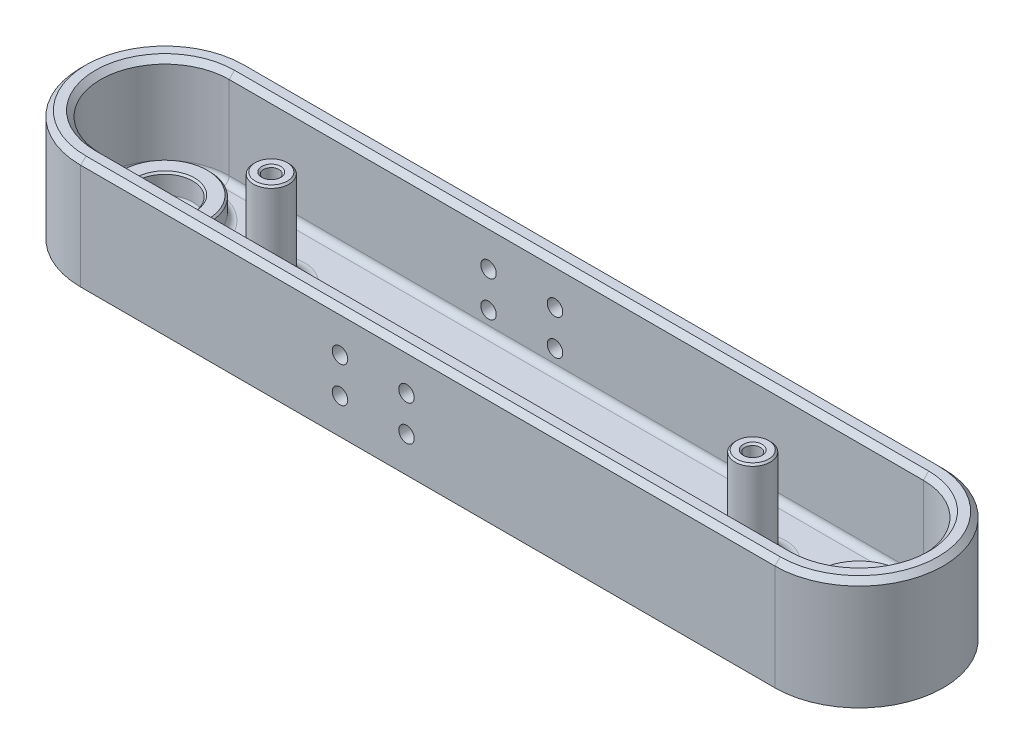
SolidWorks part; units mm, degrees
material "PLA"
ref_plane "Front Plane" through (0, 0, 0) normal (0, 0, 1) x (1, 0, 0)
ref_plane "Top Plane" through (0, 0, 0) normal (0, 1, 0) x (1, 0, 0)
ref_plane "Right Plane" through (0, 0, 0) normal (1, 0, 0) x (0, 0, -1)
sketch "Sketch1" plane through (0, 0, 0) normal (0, 1, 0) x (1, 0, 0)
  line L0 (-99.441, 0) -> (99.441, 0) construction
  line L1 (0, -55.9739) -> (0, 55.9739) construction
  line L2 (-99.441, 24.13) -> (99.441, 24.13)
  line L3 (-99.441, -24.13) -> (99.441, -24.13)
  arc A0 (-99.441, 24.13) -> (-99.441, -24.13) centre (-99.441, 0) ccw
  arc A1 (99.441, 24.13) -> (99.441, -24.13) centre (99.441, 0) cw
  point P4 (0, 0)
  point P10 (0, 0)
  dimension "D2" = 48.26
  dimension "D1" = 198.882
extrude "MainBlock" add sketch "Sketch1" along normal blind 31.75
sketch "Sketch2" plane through (0, 31.75, 0) normal (0, 1, 0) x (1, 0, 0)
  line L0 (0, 0) -> (155.7407, 0) construction
  line L1 (0, 0) -> (0, 57.4416) construction
  line L2 (-99.441, -24.13) -> (99.441, -24.13) construction
  line L3 (99.441, 24.13) -> (-99.441, 24.13) construction
  line L4 (-99.441, -24.13) -> (99.441, -24.13) construction
  line L5 (99.441, 24.13) -> (-99.441, 24.13) construction
  line L6 (-99.441, 18.415) -> (99.441, 18.415)
  line L7 (-99.441, -18.415) -> (99.441, -18.415)
  arc A0 (99.441, -24.13) -> (99.441, 24.13) centre (99.441, 0) ccw construction
  arc A1 (-99.441, 24.13) -> (-99.441, -24.13) centre (-99.441, 0) ccw construction
  arc A2 (99.441, -24.13) -> (99.441, 24.13) centre (99.441, 0) ccw construction
  arc A3 (-99.441, 24.13) -> (-99.441, -24.13) centre (-99.441, 0) ccw construction
  arc A4 (-99.441, 18.415) -> (-99.441, -18.415) centre (-99.441, 0) ccw
  arc A5 (99.441, 18.415) -> (99.441, -18.415) centre (99.441, 0) cw
  point P18 (0, 18.415)
  point P19 (0, -18.415)
  dimension "D1" = 5.715
extrude "MainPocket" cut sketch "Sketch2" against normal offset from surface (27.305 mm away) 4.445 up to face at (0, 0, 0)
sketch "Sketch3" plane through (0, 0, 0) normal (0, -1, 0) x (1, 0, 0)
  line L2 (-99.441, -24.13) -> (99.441, -24.13)
  line L3 (99.441, 24.13) -> (-99.441, 24.13)
  line L4 (-99.441, -24.13) -> (99.441, -24.13) construction
  line L5 (99.441, 24.13) -> (-99.441, 24.13) construction
  circle A0 centre (-99.441, 0) radius 4.445
  circle A1 centre (99.441, 0) radius 4.445
  arc A2 (-99.441, 24.13) -> (-99.441, -24.13) centre (-99.441, 0) ccw
  arc A3 (99.441, -24.13) -> (99.441, 24.13) centre (99.441, 0) ccw
  arc A4 (-99.441, 24.13) -> (-99.441, -24.13) centre (-99.441, 0) ccw construction
  arc A5 (99.441, -24.13) -> (99.441, 24.13) centre (99.441, 0) ccw construction
  dimension "D2" = 8.89
  dimension "D3" = 8.89
  dimension "D1" = 0
extrude "Cut-Extrude1" cut sketch "Sketch3" against normal through all
sketch "Sketch4" plane through (0, 4.445, 0) normal (0, 1, 0) x (1, 0, 0)
  line L0 (0, 0) -> (50000, 0) construction
  line L1 (0, 0) -> (0, 50000) construction
  line L2 (99.441, 18.415) -> (-99.441, 18.415)
  line L3 (-99.441, -18.415) -> (99.441, -18.415)
  line L4 (99.441, 18.415) -> (-99.441, 18.415) construction
  line L5 (-99.441, -18.415) -> (99.441, -18.415) construction
  circle A0 centre (-99.441, 0) radius 7.9566
  circle A1 centre (-99.441, 0) radius 12.7
  arc A2 (99.441, -18.415) -> (99.441, 18.415) centre (99.441, 0) ccw
  arc A3 (-99.441, 18.415) -> (-99.441, -18.415) centre (-99.441, 0) ccw
  arc A4 (99.441, -18.415) -> (99.441, 18.415) centre (99.441, 0) ccw construction
  arc A5 (-99.441, 18.415) -> (-99.441, -18.415) centre (-99.441, 0) ccw construction
  circle A6 centre (99.441, 0) radius 12.7
  circle A7 centre (99.441, 0) radius 7.9566
  dimension "D2" = 15.9131
  dimension "D3" = 25.4
  dimension "D1" = 0
extrude "Boss-Extrude1" add sketch "Sketch4" along normal blind 6.35
sketch "Sketch5" plane through (0, 0, 0) normal (0, -1, 0) x (1, 0, 0)
  line L0 (0, 0) -> (0, 50000) construction
  line L2 (-99.441, -24.13) -> (99.441, -24.13)
  line L3 (99.441, 24.13) -> (-99.441, 24.13)
  line L4 (-99.441, -24.13) -> (99.441, -24.13) construction
  line L5 (99.441, 24.13) -> (-99.441, 24.13) construction
  circle A0 centre (-99.441, 0) radius 6.35
  circle A1 centre (-99.441, 0) radius 4.445 construction
  arc A2 (-99.441, 24.13) -> (-99.441, -24.13) centre (-99.441, 0) ccw
  arc A3 (99.441, -24.13) -> (99.441, 24.13) centre (99.441, 0) ccw
  arc A4 (-99.441, 24.13) -> (-99.441, -24.13) centre (-99.441, 0) ccw construction
  arc A5 (99.441, -24.13) -> (99.441, 24.13) centre (99.441, 0) ccw construction
  circle A6 centre (-99.441, 0) radius 4.445
  circle A7 centre (99.441, 0) radius 4.445 construction
  circle A8 centre (99.441, 0) radius 6.35 construction
  dimension "D2" = 12.7
  dimension "D1" = 0
extrude "Boss-Extrude2" [suppressed] add sketch "Sketch5" along normal blind 3.81
fillet "Fillet1" [suppressed] radius 1.27
sketch "Sketch7" plane through (0, 4.445, 0) normal (0, 1, 0) x (1, 0, 0)
  line L0 (1.3556, 0) -> (50001.3556, 0) construction
  circle A0 centre (0, 0) radius 2.2225 construction
  circle A1 centre (-68.961, 0) radius 2.2225
  circle A2 centre (-99.441, 0) radius 4.445 construction
  circle A3 centre (99.441, 0) radius 4.445 construction
  circle A4 centre (99.441, 0) radius 4.445 construction
  circle A5 centre (-99.441, 0) radius 4.445 construction
  circle A6 centre (68.961, 0) radius 2.2225
  circle A7 centre (-68.961, 0) radius 5.08
  circle A8 centre (0, 0) radius 5.08 construction
  circle A9 centre (68.961, 0) radius 5.08
  dimension "D3" = 4.445
  dimension "D4" = 4.445
  dimension "D5" = 4.445
  dimension "D6" = 10.16
  dimension "D7" = 10.16
  dimension "D8" = 10.16
  dimension "D1" = 30.48
  dimension "D2" = 30.48
extrude "Boss-Extrude3" add sketch "Sketch7" along normal up to surface (27.305 mm away) up to face at (0, 31.75, 0)
fillet "Fillet2" radius 0.635 2 edges at (99.441, 4.445, 7.9566) (-99.441, 4.445, 7.9566)
fillet "Fillet3" radius 1.905 6 edges at (117.856, 4.445, 0) (0, 4.445, 18.415) (-117.856, 4.445, 0) (99.441, 4.445, -12.7) (-99.441, 4.445, 12.7) (0, 4.445, -18.415)
fillet "Fillet6" radius 4.445 2 edges at (68.961, 4.445, 5.08) (-68.961, 4.445, 5.08)
sketch "Sketch9" plane through (0, 0, 0) normal (0, -1, 0) x (1, 0, 0)
  circle A0 centre (99.441, 0) radius 4.445 construction
  circle A1 centre (99.441, 0) radius 4.445
  circle A6 centre (99.441, 0) radius 5.715
  dimension "D2" = 11.43
extrude "Bearing-Spacer" [suppressed] add sketch "Sketch9" along normal blind 8.89
fillet "Fillet7" [suppressed] radius 2.54
chamfer "Chamfer1" [suppressed] distance 0.508 angle 45
chamfer "Chamfer2" distance 0.508 angle 45 10 edges at (68.961, 31.75, 2.2225) (99.441, 4.445, 4.445) (99.441, 10.795, -12.7) (99.441, 10.795, -7.9566) (-99.441, 4.445, 4.445) (-99.441, 10.795, 12.7) (-68.961, 31.75, 5.08) (68.961, 31.75, 5.08) (-99.441, 10.795, 7.9566) (-68.961, 31.75, 2.2225)
sketch "Sketch12" plane through (0, 0, 0) normal (0, 1, 0) x (1, 0, 0)
  line L0 (-34.671, 24.13) -> (-24.511, 35.56)
  line L1 (99.441, 24.13) -> (-99.441, 24.13) construction
  line L2 (-18.161, 29.21) -> (-18.161, 24.13) construction
  line L3 (-24.511, 35.56) -> (-11.811, 35.56)
  line L4 (-34.671, 24.13) -> (-1.651, 24.13)
  line L5 (-1.651, 24.13) -> (-11.811, 35.56)
  circle A0 centre (-18.161, 29.21) radius 2.0066
  circle A1 centre (-99.441, 0) radius 4.445 construction
  point P9 (-18.161, 35.56)
  dimension "D5" = 4.0132
  dimension "D1" = 33.02
  dimension "D2" = 12.7
  dimension "D3" = 29.21
  dimension "D4" = 11.43
  dimension "D6" = 81.28
extrude "Stab_bar_Mount" [suppressed] add sketch "Sketch12" along normal blind 25.4
chamfer "Chamfer3" distance 1.524 angle 45 8 edges at (0, 31.75, -24.13) (-123.571, 31.75, 0) (123.571, 31.75, 0) (0, 31.75, 24.13) (0, 31.75, -18.415) (-117.856, 31.75, 0) (117.856, 31.75, 0) (0, 31.75, 18.415)
chamfer "Chamfer5" [suppressed] distance 0.381 angle 45
sketch "Sketch10" plane through (0, 4.445, 0) normal (0, 1, 0) x (1, 0, 0)
  circle A0 centre (68.961, 0) radius 2.2225 construction
  circle A2 centre (-68.961, 0) radius 2.2225 construction
  circle A3 centre (68.961, 0) radius 2.2225
  circle A4 centre (0, 0) radius 2.2225 construction
  circle A5 centre (-68.961, 0) radius 2.2225
extrude "Boss-Extrude4" add sketch "Sketch10" along normal blind 16.51
fillet "Fillet8" [suppressed] radius 5.08
sketch "Sketch13" plane through (0, 0, -24.13) normal (0, 0, -1) x (-1, 0, 0)
  line L0 (6.096, 20.32) -> (25.146, 20.32) construction
  line L1 (25.146, 20.32) -> (25.146, 10.16) construction
  line L2 (25.146, 10.16) -> (6.096, 10.16) construction
  line L3 (6.096, 10.16) -> (6.096, 20.32) construction
  line L4 (15.621, 20.32) -> (15.621, 10.16) construction
  line L5 (6.096, 15.24) -> (25.146, 15.24) construction
  line L6 (-99.441, 0) -> (99.441, 0) construction
  line L7 (99.441, 30.226) -> (99.441, 0) construction
  circle A0 centre (25.146, 20.32) radius 2.2225
  circle A1 centre (6.096, 20.32) radius 2.2225
  circle A2 centre (6.096, 10.16) radius 2.2225
  circle A3 centre (25.146, 10.16) radius 2.2225
  dimension "D3" = 4.445
  dimension "D1" = 19.05
  dimension "D2" = 10.16
  dimension "D4" = 15.24
  dimension "D5" = 83.82
extrude "Stabilizer-Bar-MountHoles" cut sketch "Sketch13" against normal up to surface (5.715 mm away) up to face at (0, 18.288, -18.415)
mirror "Mirror1" about plane through (0, 0, 0) normal (0, 0, 1) of "Stabilizer-Bar-MountHoles"
equation "\"D5@Sketch7\"=\"D3@Sketch7\""
equation "\"D4@Sketch7\"=\"D3@Sketch7\""
equation "\"D7@Sketch7\"=\"D6@Sketch7\""
equation "\"D8@Sketch7\"=\"D6@Sketch7\""
